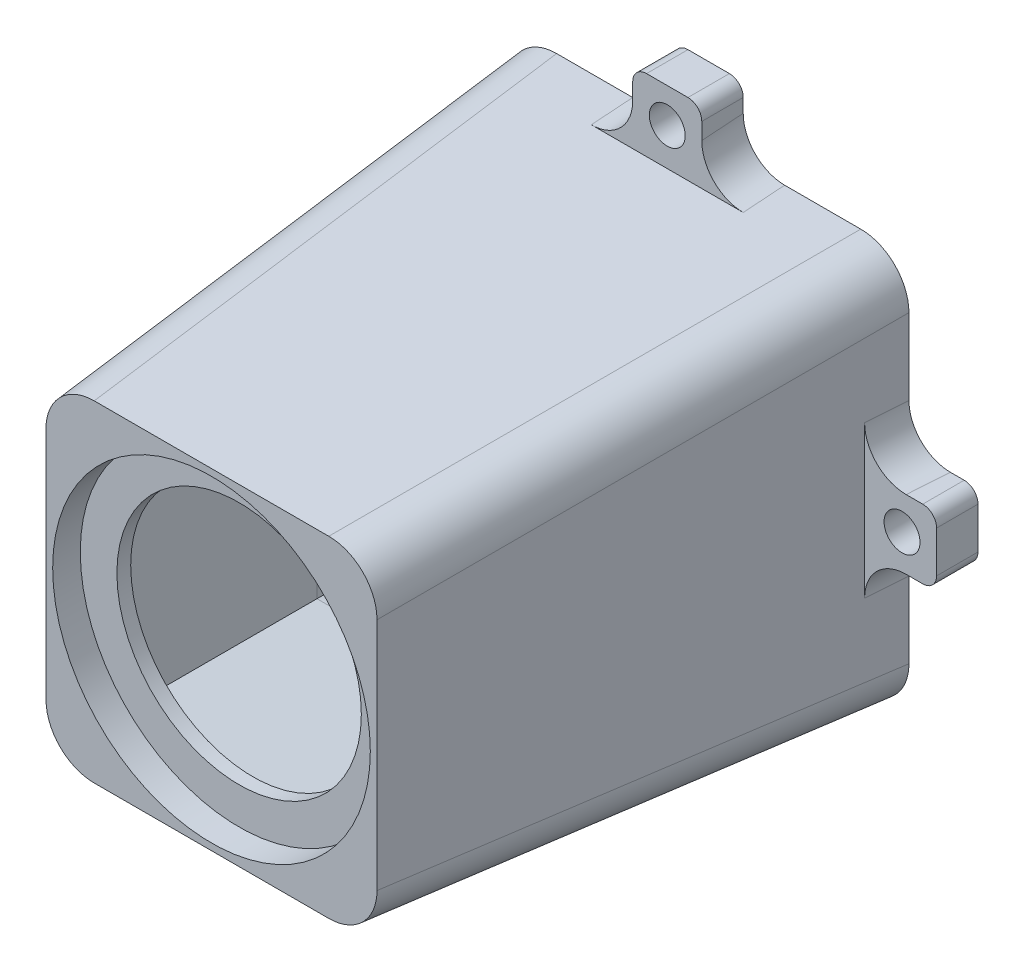
SolidWorks part; units mm, degrees
ref_plane "Спереди" through (0, 0, 0) normal (0, 0, 1) x (1, 0, 0)
ref_plane "Сверху" through (0, 0, 0) normal (0, 1, 0) x (1, 0, 0)
ref_plane "Справа" through (0, 0, 0) normal (1, 0, 0) x (0, 0, -1)
sketch "Эскиз1" plane through (0, 0, 0) normal (0, 0, 1) x (1, 0, 0)
  line L0 (-14.5, -14.5) -> (-14.5, 14.5)
  line L1 (-11.5, -11.5) -> (11.5, -11.5) construction
  line L2 (-11.5, -11.5) -> (-11.5, 11.5) construction
  line L3 (-11.5, 11.5) -> (11.5, 11.5) construction
  line L4 (11.5, -11.5) -> (11.5, 11.5) construction
  line L5 (-11.5, -11.5) -> (11.5, 11.5) construction
  line L6 (-11.5, 11.5) -> (11.5, -11.5) construction
  line L7 (-14.5, 14.5) -> (14.5, 14.5)
  line L8 (14.5, -14.5) -> (14.5, 14.5)
  line L9 (-14.5, -14.5) -> (14.5, -14.5)
  point P0 (0, 0)
  dimension "D1" = 23
  dimension "D2" = 3
extrude "Бобышка-Вытянуть1" add sketch "Эскиз1" along normal blind 36 draft 4
shell "Оболочка1" thickness 3 removed face at (0, 0, 0)
sketch "Эскиз3" plane through (0, 0, 0) normal (0, 0, -1) x (-1, 0, 0)
  line L1 (-11.15, -11.15) -> (11.15, -11.15)
  line L2 (-11.15, -11.15) -> (-11.15, 11.15)
  line L3 (-11.15, 11.15) -> (11.15, 11.15)
  line L4 (11.15, -11.15) -> (11.15, 11.15)
  line L5 (-11.15, -11.15) -> (11.15, 11.15) construction
  line L6 (-11.15, 11.15) -> (11.15, -11.15) construction
  point P0 (0, 0)
  dimension "D1" = 22.3
extrude "Вырез-Вытянуть2" cut sketch "Эскиз3" against normal blind 16
fillet "Скругление1" radius 3.5 4 edges at (10.3738, 0, 16) (0, -10.3738, 16) (-10.3738, 0, 16) (0, 10.3738, 16)
fillet "Скругление2" radius 3.5 4 edges at (13.2413, -13.2413, 18) (-13.2413, -13.2413, 18) (-13.2413, 13.2413, 18) (13.2413, 13.2413, 18)
sketch "Эскиз4" plane through (0, 0, 36) normal (0, 0, 1) x (1, 0, 0)
  circle A0 centre (0, 0) radius 8.85
  dimension "D1" = 17.7
extrude "Вырез-Вытянуть3" cut sketch "Эскиз4" against normal up to surface (3 mm away) up to face at (0, 0, 33)
sketch "Эскиз5" plane through (0, 0, 36) normal (0, 0, 1) x (1, 0, 0)
  circle A0 centre (0, 0) radius 11.5
  dimension "D1" = 23
extrude "Вырез-Вытянуть4" cut sketch "Эскиз5" against normal blind 2
sketch "Эскиз6" plane through (0, 0, 0) normal (0, 0, -1) x (-1, 0, 0)
  line L0 (0, 0) -> (14.5, 0) construction
  line L1 (14.5, 11.0085) -> (14.5, -11.0085) construction
  line L2 (14.5, 0) -> (19.5, 0) construction
  line L3 (13.2, -2.5) -> (19.5, -2.5)
  line L5 (13.2, 2.5) -> (19.5, 2.5)
  line L6 (19.5, -2.5) -> (19.5, 2.5)
  line L7 (-2.5, -13.2) -> (-2.5, -19.5)
  line L8 (-2.5, -19.5) -> (2.5, -19.5)
  line L9 (13.2, 2.5) -> (13.2, -2.5)
  line L22 (2.5, -13.2) -> (2.5, -19.5)
  line L23 (2.5, -13.2) -> (-2.5, -13.2)
  line L24 (-13.2, 2.5) -> (-19.5, 2.5)
  line L25 (-19.5, 2.5) -> (-19.5, -2.5)
  line L26 (-13.2, -2.5) -> (-19.5, -2.5)
  line L27 (-13.2, -2.5) -> (-13.2, 2.5)
  line L28 (2.5, 13.2) -> (2.5, 19.5)
  line L29 (2.5, 19.5) -> (-2.5, 19.5)
  line L30 (-2.5, 13.2) -> (-2.5, 19.5)
  line L31 (-2.5, 13.2) -> (2.5, 13.2)
  circle A0 centre (17, 0) radius 1.3
  circle A4 centre (0, -17) radius 1.3
  circle A5 centre (-17, 0) radius 1.3
  circle A6 centre (0, 17) radius 1.3
  point P33 (0, 0)
  point P35 (0, 0)
  dimension "D3" = 2.6
  dimension "D1" = 4
  dimension "D2" = 5
  dimension "D4" = 1.3
  dimension "D5" = 5
extrude "Бобышка-Вытянуть2" add sketch "Эскиз6" against normal blind 3
fillet "Скругление3" radius 3 8 edges at (14.3951, 2.5, 1.5) (14.3951, -2.5, 1.5) (2.5, -14.3951, 1.5) (-2.5, -14.3951, 1.5) (-14.3951, -2.5, 1.5) (-14.3951, 2.5, 1.5) (-2.5, 14.3951, 1.5) (2.5, 14.3951, 1.5)
fillet "Скругление4" radius 1 8 edges at (19.5, -2.5, 1.5) (2.5, -19.5, 1.5) (-2.5, -19.5, 1.5) (-19.5, -2.5, 1.5) (-19.5, 2.5, 1.5) (-2.5, 19.5, 1.5) (2.5, 19.5, 1.5) (19.5, 2.5, 1.5)
